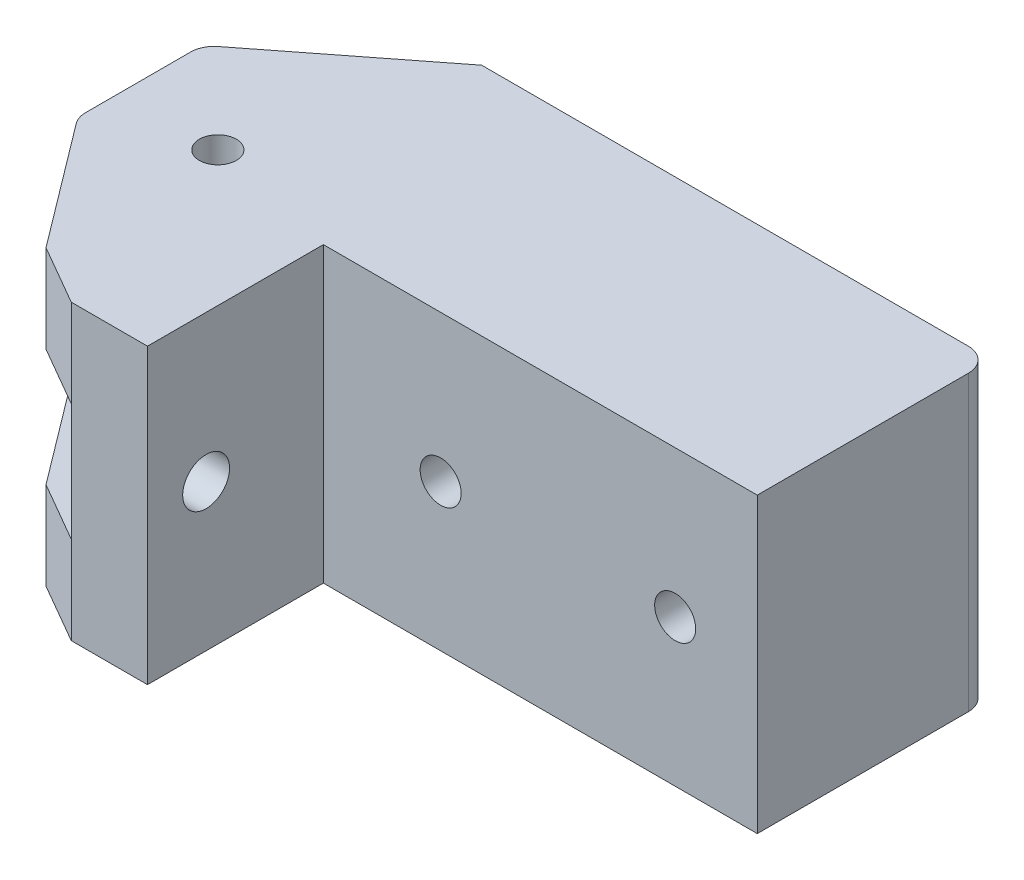
SolidWorks part; units mm, degrees
ref_plane "Front Plane" through (0, 0, 0) normal (0, 0, 1) x (1, 0, 0)
ref_plane "Top Plane" through (0, 0, 0) normal (0, 1, 0) x (1, 0, 0)
ref_plane "Right Plane" through (0, 0, 0) normal (1, 0, 0) x (0, 0, -1)
sketch "Sketch1" plane through (0, 0, 0) normal (0, 1, 0) x (1, 0, 0)
  line L0 (0, 0) -> (-43.5, 0)
  line L1 (-43.5, 0) -> (-43.5, -35) construction
  line L2 (-43.5, -35) -> (-37, -35)
  line L3 (-37, -35) -> (-37, -20)
  line L4 (-37, -20) -> (0, -20)
  line L5 (0, -20) -> (0, 0)
  line L6 (-43.5, 0) -> (-56.8853, -10.4577)
  line L7 (-56.8853, -10.4577) -> (-56.8853, -21.0577)
  line L8 (-56.8853, -21.0577) -> (-48.5962, -32.0577)
  line L9 (-48.5962, -32.0577) -> (-43.5, -35)
  line L10 (-43.5, -17.5) -> (-48.5, -17.5) construction
  circle A0 centre (-48.5, -17.5) radius 1.575
  dimension "D11" = 3.15
  dimension "D1" = 43.5
  dimension "D2" = 35
  dimension "D3" = 20
  dimension "D4" = 37
  dimension "D5" = 30
  dimension "D6" = 38
  dimension "D7" = 10.6
  dimension "D8" = 37
  dimension "D9" = 11
  dimension "D10" = 5
extrude "Boss-Extrude1" add sketch "Sketch1" along normal mid plane 25
sketch "Sketch2" plane through (0, 0, 35) normal (0, 0, 1) x (1, 0, 0)
  line L0 (-43.5, 12.5) -> (-43.5, -12.5) construction
  line L1 (-43.5, -5) -> (-56.8853, -5)
  line L2 (-43.5, -5) -> (-43.5, 5)
  line L3 (-43.5, 5) -> (-56.8853, 5)
  line L4 (-56.8853, -5) -> (-56.8853, 5)
  line L5 (-56.8853, 12.5) -> (-56.8853, -12.5) construction
  line L6 (-56.8853, 12.5) -> (-48.5962, 12.5) construction
  dimension "D1" = 7.5
  dimension "D2" = 10
extrude "Cut-Extrude1" cut sketch "Sketch2" against normal through all
sketch "Sketch3" plane through (0, 0, 20) normal (0, 0, 1) x (1, 0, 0)
  line L1 (0, 0) -> (-27, 0) construction
  line L2 (-37, 12.5) -> (-37, -12.5) construction
  circle A0 centre (-27, 0) radius 1.75
  circle A1 centre (-7, 0) radius 1.75
  dimension "D1" = 3.5
  dimension "D2" = 20
  dimension "D3" = 10
extrude "Cut-Extrude2" cut sketch "Sketch3" against normal blind 25
sketch "Sketch4" plane through (0, 0, 0) normal (0, 0, -1) x (-1, 0, 0)
  circle A0 centre (7, 0) radius 4
  circle A2 centre (27, 0) radius 4
extrude "Cut-Extrude3" cut sketch "Sketch4" against normal blind 4
fillet "Fillet1" radius 2 5 edges at (0, 0, 0) (-56.8853, 8.75, 10.4577) (-56.8853, 8.75, 21.0577) (-56.8853, -8.75, 21.0577) (-56.8853, -8.75, 10.4577)
sketch "Sketch5" plane through (-43.5, 0, 0) normal (-1, 0, 0) x (0, 0, 1)
  line L0 (30, -12.5) -> (30, 12.5) construction
  line L3 (35, -5) -> (35, 5) construction
  line L4 (21.5922, 12.5) -> (32.0577, 12.5) construction
  line L5 (21.5922, -12.5) -> (32.0577, -12.5) construction
  circle A0 centre (30, 0) radius 2
  point P6 (30, 12.5)
  point P8 (26.8249, 0)
  point P10 (30, -12.5)
  dimension "D1" = 4
  dimension "D2" = 5
sketch "Sketch6" plane through (0, 12.5, 0) normal (0, 1, 0) x (1, 0, 0)
  line L0 (-37, -35) -> (-37, -20)
extrude "Cut-Extrude4" cut sketch "Sketch5" against normal blind 10
sketch "Sketch7" plane through (-43.5, 0, 0) normal (-1, 0, 0) x (0, 0, 1)
  circle A0 centre (30, 0) radius 3.575
  dimension "D1" = 7.15
extrude "Cut-Extrude5" cut sketch "Sketch7" against normal blind 3.5
